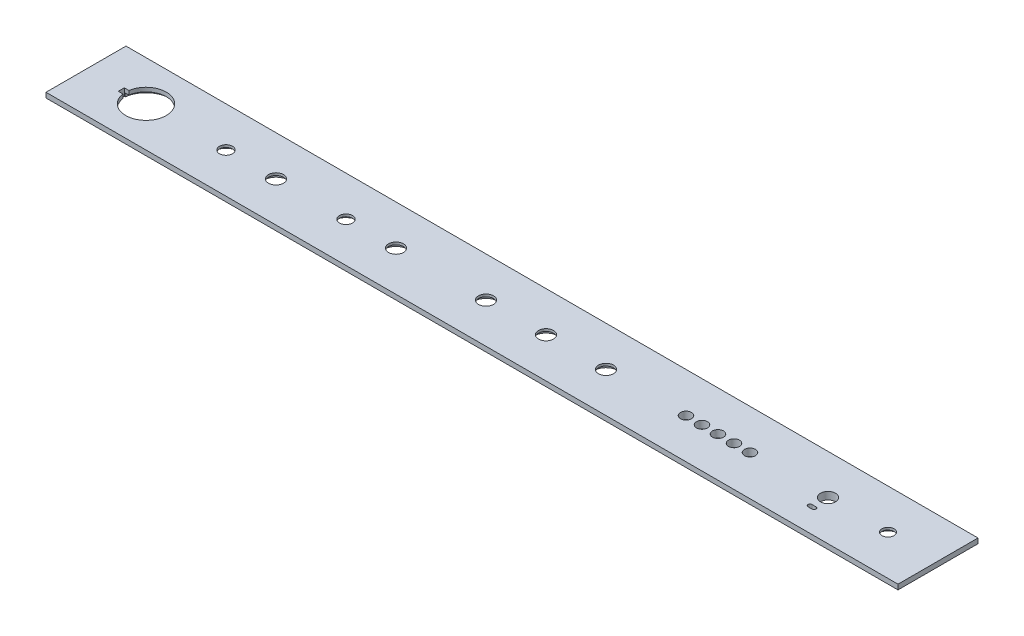
SolidWorks part; units mm, degrees
ref_plane "Спереди" through (0, 0, 0) normal (0, 0, 1) x (1, 0, 0)
ref_plane "Сверху" through (0, 0, 0) normal (0, 1, 0) x (1, 0, 0)
ref_plane "Справа" through (0, 0, 0) normal (1, 0, 0) x (0, 0, -1)
sketch "Эскиз1" plane through (0, 0, 0) normal (0, 1, 0) x (1, 0, 0)
  line L1 (-213, 20) -> (213, 20)
  line L2 (-213, 20) -> (-213, -20)
  line L3 (-213, -20) -> (213, -20)
  line L4 (213, 20) -> (213, -20)
  line L5 (-213, 20) -> (213, -20) construction
  line L6 (-213, -20) -> (213, 20) construction
  point P0 (0, 0)
  dimension "D1" = 40
  dimension "D2" = 426
extrude "Бобышка-Вытянуть1" add sketch "Эскиз1" along normal blind 3.7
extrude "Вырез-Вытянуть-Тонкостенный1" cut sketch "Эскиз1<2>" along normal blind 1.2 thin thin type one direction reverse wall 1.6
sketch "Эскиз1<2>" plane through (0, 0, 0) normal (0, 1, 0) x (1, 0, 0) same geometry as "Эскиз1"
sketch "Эскиз2" plane through (0, 0, 0) normal (0, 1, 0) x (1, 0, 0)
  line L0 (157, -8) -> (159, -8) construction
  line L1 (213, 20) -> (213, -20) construction
  line L2 (157, -7) -> (159, -7)
  line L3 (157, -9) -> (159, -9)
  line L4 (-213, 20) -> (-213, -20) construction
  line L5 (95, 0) -> (103, 0) construction
  line L6 (103, 0) -> (111, 0) construction
  line L7 (111, 0) -> (119, 0) construction
  line L8 (-193.0386, -1.5) -> (-195.35, -1.5)
  line L9 (-195.35, -1.5) -> (-195.35, 1.5)
  line L10 (-195.35, 1.5) -> (-193.0386, 1.5)
  line L11 (95, 0) -> (87, 0) construction
  circle A1 centre (158, 0) radius 3.75
  circle A3 centre (188, 0) radius 3
  arc A4 (157, -7) -> (157, -9) centre (157, -8) ccw
  arc A5 (159, -9) -> (159, -7) centre (159, -8) ccw
  circle A6 centre (-13, 0) radius 3.75
  circle A7 centre (17, 0) radius 3.75
  circle A8 centre (47, 0) radius 3.75
  circle A9 centre (-58, 0) radius 3.75
  circle A10 centre (-83, 0) radius 3.25
  circle A11 centre (-118, 0) radius 3.75
  circle A12 centre (-143, 0) radius 3.25
  circle A13 centre (95, 0) radius 2.75
  circle A14 centre (103, 0) radius 2.75
  circle A15 centre (111, 0) radius 2.75
  circle A16 centre (119, 0) radius 2.75
  circle A17 centre (-183, 0) radius 10.15
  circle A18 centre (87, 0) radius 2.75
  circle A19 centre (87, 0) radius 3.75 construction
  circle A20 centre (95, 0) radius 3.75 construction
  circle A21 centre (-13, 0) radius 6.25
  circle A22 centre (17, 0) radius 6.25
  circle A23 centre (47, 0) radius 6.25
  circle A24 centre (-118, 0) radius 6.25
  circle A25 centre (-58, 0) radius 6.25
  point P6 (158, -8)
  point P9 (213, 0)
  point P40 (-213, 0)
  point P41 (107, 0)
  point P45 (-195.35, 0)
  point P48 (-183, 10.15)
  point P49 (-172.85, 0)
  dimension "D1" = 7.5
  dimension "D2" = 25
  dimension "D3" = 6
  dimension "D7" = 1
  dimension "D11" = 6.5
  dimension "D12" = 70
  dimension "D16" = 5.5
  dimension "D19" = 20.3
  dimension "D23" = 7.5
  dimension "D24" = 12.5
  dimension "D4" = 30
  dimension "D5" = 8
  dimension "D6" = 2
  dimension "D8" = 30
  dimension "D9" = 30
  dimension "D10" = 230
  dimension "D13" = 25
  dimension "D14" = 35
  dimension "D15" = 25
  dimension "D17" = 32
  dimension "D18" = 106
  dimension "D20" = 3
  dimension "D21" = 22.5
  dimension "D22" = 30
extrude "Вырез-Вытянуть1" cut sketch "Эскиз2" along normal blind 10 contours A17 | A17 L9 | A12 | A11 | A10 | A9 | A6 | A7 | A8 | A13 | A14 | A16 | A3 | L3 A5 L2 A4 | A18 | A15 | A1 region at (158, 0, 8) region at (-194.2312, 0, 0) region at (-183, 0, 0) region at (188, 0, 0) region at (-13, 0, 0) region at (17, 0, 0) region at (47, 0, 0) region at (-58, 0, 0) region at (-83, 0, 0) region at (-118, 0, 0) region at (-143, 0, 0) region at (95, 0, 0) region at (103, 0, 0) region at (119, 0, 0) region at (87, 0, 0)
sketch "Эскиз4" plane through (0, 0, 0) normal (0, 1, 0) x (1, 0, 0)
  circle A0 centre (-183, 0) radius 12
  dimension "D1" = 24
extrude "Вырез-Вытянуть2" cut sketch "Эскиз4" along normal offset from surface (1.7 mm away) 2 up to face at (-189.1471, 3.7, 0)
extrude "Вырез-Вытянуть-Тонкостенный2" cut sketch "Эскиз2<3>" along normal offset from surface (2.5 mm away) 1.2 from surface thin contours A12 | A10 | A3 up to face at (-189.1471, 3.7, 0) starting at face at (-189.1515, 0, 0) thin type one direction wall 3
sketch "Эскиз2<3>" plane through (0, 0, 0) normal (0, 1, 0) x (1, 0, 0) same geometry as "Эскиз2"
sketch "Эскиз3" plane through (0, 0, 0) normal (0, 1, 0) x (1, 0, 0)
  line L1 (-152, -15) -> (-109, -15)
  line L2 (-158, -9) -> (-158, 9)
  line L3 (-152, 15) -> (-109, 15)
  line L4 (-103, -9) -> (-103, 9)
  line L5 (-213, -20) -> (213, -20) construction
  line L10 (-152, -13.5) -> (-109, -13.5)
  line L11 (-104.5, -9) -> (-104.5, 9)
  line L12 (-152, 13.5) -> (-109, 13.5)
  line L13 (-156.5, -9) -> (-156.5, 9)
  line L26 (-22, -13.5) -> (56, -13.5)
  line L27 (-22, -15) -> (56, -15)
  line L28 (-28, -9) -> (-28, 9)
  line L29 (-22, 15) -> (56, 15)
  line L30 (62, -9) -> (62, 9)
  line L31 (83, -15) -> (123, -15)
  line L32 (77, -9) -> (77, 9)
  line L33 (83, 15) -> (123, 15)
  line L34 (129, -9) -> (129, 9)
  line L35 (146, -15) -> (196, -15)
  line L36 (140, -9) -> (140, 9)
  line L37 (146, 15) -> (196, 15)
  line L38 (202, -9) -> (202, 9)
  line L39 (60.5, -9) -> (60.5, 9)
  line L40 (-22, 13.5) -> (56, 13.5)
  line L41 (-26.5, -9) -> (-26.5, 9)
  line L42 (83, -13.5) -> (123, -13.5)
  line L43 (127.5, -9) -> (127.5, 9)
  line L44 (83, 13.5) -> (123, 13.5)
  line L45 (78.5, -9) -> (78.5, 9)
  line L46 (146, -13.5) -> (196, -13.5)
  line L47 (200.5, -9) -> (200.5, 9)
  line L48 (146, 13.5) -> (196, 13.5)
  line L49 (141.5, -9) -> (141.5, 9)
  line L50 (-197, -13.5) -> (-169, -13.5)
  line L51 (-92, -15) -> (-49, -15)
  line L52 (-98, -9) -> (-98, 9)
  line L53 (-92, 15) -> (-49, 15)
  line L54 (-43, -9) -> (-43, 9)
  line L55 (-197, -15) -> (-169, -15)
  line L56 (-203, -9) -> (-203, 9)
  line L57 (-197, 15) -> (-169, 15)
  line L58 (-163, -9) -> (-163, 9)
  line L59 (-164.5, -9) -> (-164.5, 9)
  line L60 (-197, 13.5) -> (-169, 13.5)
  line L61 (-201.5, -9) -> (-201.5, 9)
  line L62 (-92, -13.5) -> (-49, -13.5)
  line L63 (-44.5, -9) -> (-44.5, 9)
  line L64 (-92, 13.5) -> (-49, 13.5)
  line L65 (-96.5, -9) -> (-96.5, 9)
  arc A0 (-109, -15) -> (-103, -9) centre (-109, -9) ccw
  arc A1 (-103, 9) -> (-109, 15) centre (-109, 9) ccw
  arc A2 (-152, 15) -> (-158, 9) centre (-152, 9) ccw
  arc A3 (-158, -9) -> (-152, -15) centre (-152, -9) ccw
  arc A8 (-109, -13.5) -> (-104.5, -9) centre (-109, -9) ccw
  arc A9 (-104.5, 9) -> (-109, 13.5) centre (-109, 9) ccw
  arc A10 (-152, 13.5) -> (-156.5, 9) centre (-152, 9) ccw
  arc A11 (-156.5, -9) -> (-152, -13.5) centre (-152, -9) ccw
  arc A24 (140, 9) -> (146, 15) centre (146, 9) cw
  arc A25 (196, 15) -> (202, 9) centre (196, 9) cw
  arc A26 (202, -9) -> (196, -15) centre (196, -9) cw
  arc A27 (140, -9) -> (146, -15) centre (146, -9) ccw
  arc A28 (77, 9) -> (83, 15) centre (83, 9) cw
  arc A29 (123, 15) -> (129, 9) centre (123, 9) cw
  arc A30 (129, -9) -> (123, -15) centre (123, -9) cw
  arc A31 (56, -15) -> (62, -9) centre (56, -9) ccw
  arc A32 (77, -9) -> (83, -15) centre (83, -9) ccw
  arc A33 (62, 9) -> (56, 15) centre (56, 9) ccw
  arc A34 (-22, 15) -> (-28, 9) centre (-22, 9) ccw
  arc A35 (-28, -9) -> (-22, -15) centre (-22, -9) ccw
  arc A36 (56, -13.5) -> (60.5, -9) centre (56, -9) ccw
  arc A37 (60.5, 9) -> (56, 13.5) centre (56, 9) ccw
  arc A38 (-22, 13.5) -> (-26.5, 9) centre (-22, 9) ccw
  arc A39 (-26.5, -9) -> (-22, -13.5) centre (-22, -9) ccw
  arc A40 (127.5, -9) -> (123, -13.5) centre (123, -9) cw
  arc A41 (123, 13.5) -> (127.5, 9) centre (123, 9) cw
  arc A42 (78.5, 9) -> (83, 13.5) centre (83, 9) cw
  arc A43 (78.5, -9) -> (83, -13.5) centre (83, -9) ccw
  arc A44 (200.5, -9) -> (196, -13.5) centre (196, -9) cw
  arc A45 (196, 13.5) -> (200.5, 9) centre (196, 9) cw
  arc A46 (141.5, 9) -> (146, 13.5) centre (146, 9) cw
  arc A47 (141.5, -9) -> (146, -13.5) centre (146, -9) ccw
  arc A48 (-49, -15) -> (-43, -9) centre (-49, -9) ccw
  arc A49 (-43, 9) -> (-49, 15) centre (-49, 9) ccw
  arc A50 (-92, 15) -> (-98, 9) centre (-92, 9) ccw
  arc A51 (-98, -9) -> (-92, -15) centre (-92, -9) ccw
  arc A52 (-169, -15) -> (-163, -9) centre (-169, -9) ccw
  arc A53 (-163, 9) -> (-169, 15) centre (-169, 9) ccw
  arc A54 (-197, 15) -> (-203, 9) centre (-197, 9) ccw
  arc A55 (-203, -9) -> (-197, -15) centre (-197, -9) ccw
  arc A56 (-169, -13.5) -> (-164.5, -9) centre (-169, -9) ccw
  arc A57 (-164.5, 9) -> (-169, 13.5) centre (-169, 9) ccw
  arc A58 (-197, 13.5) -> (-201.5, 9) centre (-197, 9) ccw
  arc A59 (-201.5, -9) -> (-197, -13.5) centre (-197, -9) ccw
  arc A60 (-49, -13.5) -> (-44.5, -9) centre (-49, -9) ccw
  arc A61 (-44.5, 9) -> (-49, 13.5) centre (-49, 9) ccw
  arc A62 (-92, 13.5) -> (-96.5, 9) centre (-92, 9) ccw
  arc A63 (-96.5, -9) -> (-92, -13.5) centre (-92, -9) ccw
  dimension "D1" = 6
  dimension "D9" = 6
  dimension "D2" = 6
  dimension "D6" = 6
  dimension "D3" = 5
  dimension "D4" = 15
  dimension "D5" = 15
  dimension "D10" = 15
  dimension "D11" = 15
  dimension "D12" = 10
  dimension "D13" = 10
  dimension "D15" = 15
  dimension "D16" = 15
  dimension "D17" = 20
  dimension "D18" = 20
  dimension "D19" = 18
  dimension "D20" = 14
  dimension "D7" = 1.5
  dimension "D14" = 1.5
  dimension "D8" = 1.5
extrude "Бобышка-Вытянуть2" add sketch "Эскиз3" against normal blind 0.1
extrude "Вырез-Вытянуть3" cut sketch "Эскиз2<5>" along normal offset from surface (2.5 mm away) 1.2 contours A21 | A22 | A23 | A25 | A24 up to face at (-189.1471, 3.7, 0)
sketch "Эскиз2<5>" plane through (0, 0, 0) normal (0, 1, 0) x (1, 0, 0) same geometry as "Эскиз2"
